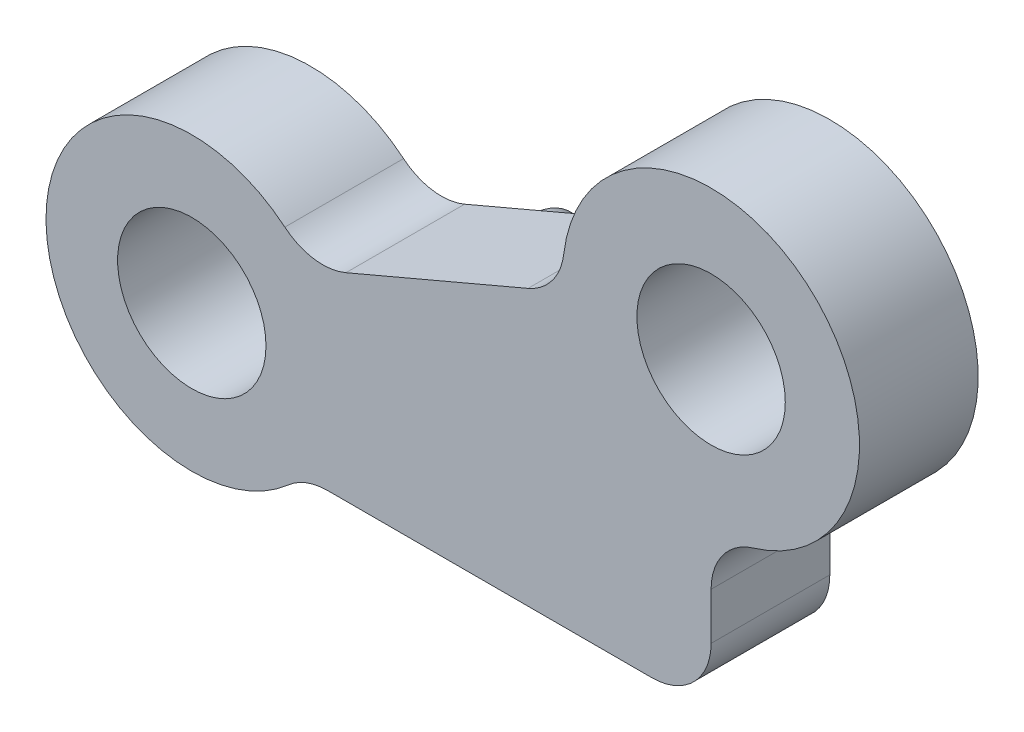
SolidWorks part; units mm, degrees
ref_plane "Front Plane" through (0, 0, 0) normal (0, 0, 1) x (1, 0, 0)
ref_plane "Top Plane" through (0, 0, 0) normal (0, 1, 0) x (1, 0, 0)
ref_plane "Right Plane" through (0, 0, 0) normal (1, 0, 0) x (0, 0, -1)
sketch "Sketch1" plane through (0, 0, 0) normal (0, 0, 1) x (1, 0, 0)
  line L0 (143.3333, 493) -> (716.6667, 493) construction
  line L1 (56.8391, 28.5799) -> (56.8391, 23.2923)
  line L2 (56.8391, 23.2923) -> (43.0826, 23.2923)
  line L3 (51.8645, 33.076) -> (43.2731, 29.4209)
  circle A2 centre (39.3406, 26.4759) radius 2.5
  circle A3 centre (56.8391, 33.5799) radius 2.5
  arc A4 (56.8391, 28.5799) -> (51.8645, 33.076) centre (56.8391, 33.5799) ccw
  arc A5 (43.2731, 29.4209) -> (43.0826, 23.2923) centre (39.3406, 26.4759) ccw
extrude "Boss-Extrude1" add sketch "Sketch1" along normal blind 4
fillet "Fillet1" radius 2 5 edges at (43.0826, 23.2923, 2) (56.8391, 23.2923, 2) (56.8391, 28.5799, 2) (43.2731, 29.4209, 2) (51.8645, 33.076, 2)
sketch "Sketch2" plane through (0, 0, 4) normal (0, 0, 1) x (1, 0, 0)
  circle A0 centre (46.1838, 27.3596) radius 1
ref_plane "Plane1" through (0, 27, 0) normal (0, 1, 0) x (1, 0, 0)
sketch "Sketch3" plane through (0, 27, 0) normal (0, 1, 0) x (1, 0, 0)
  line L3 (43.9144, 0) -> (51.3408, 0)
  line L4 (44.5353, 0) -> (42.476, 0) construction
  line L5 (51.8742, 0) -> (50.6713, 0) construction
  circle A2 centre (47.5939, 1.6244) radius 1.45
  arc A3 (49.5536, 2.0239) -> (45.6196, 1.9442) centre (47.5939, 1.6244) ccw
  spline S2 degree 3 poles (45.6196, 1.9442) (45.248, 0.9007) (44.6796, 0.2526) (43.9144, 0) knots 0.088144 0.088144 0.088144 0.088144 0.644612 0.644612 0.644612 0.644612
  spline S3 degree 3 poles (49.5536, 2.0239) (49.9528, 0.9456) (50.5485, 0.271) (51.3408, 0) knots 0.072893 0.072893 0.072893 0.072893 0.627566 0.627566 0.627566 0.627566
  dimension "D2" = 2.9
  dimension "D3" = 4
ref_plane "Plane2" through (0, 0, 2) normal (0, 0, 1) x (1, 0, 0)
ref_plane "Plane3" through (45, 0, 0) normal (1, 0, 0) x (0, 0, -1)
sketch "Sketch7" plane through (45, 0, 0) normal (1, 0, 0) x (0, 0, -1)
  line L0 (3.6244, 27) -> (1.9442, 27) construction
  line L1 (2.0239, 27) -> (0, 27) construction
  line L2 (0, 21.5629) -> (0, 31.389) construction
  line L3 (0, 30.085) -> (0, 23.2923)
  circle A0 centre (1.6865, 27) radius 1.45
  arc A1 (1.6865, 24.9982) -> (1.6865, 29.0018) centre (1.6865, 27) ccw
  spline S0 degree 2 poles (1.6865, 29.0018) (0.6922, 29.3421) (0, 30.085) knots 0 0 0 1 1 1
  spline S1 degree 2 poles (1.6865, 24.9982) (0.3217, 24.5633) (0, 23.2923) knots 0 0 0 1 1 1
  point P7 (0, 30.085)
  dimension "D1" = 2.9
extrude "Boss-Extrude4" add sketch "Sketch7" along normal blind 2
equation "\"D1@Fillet1\"=2"
